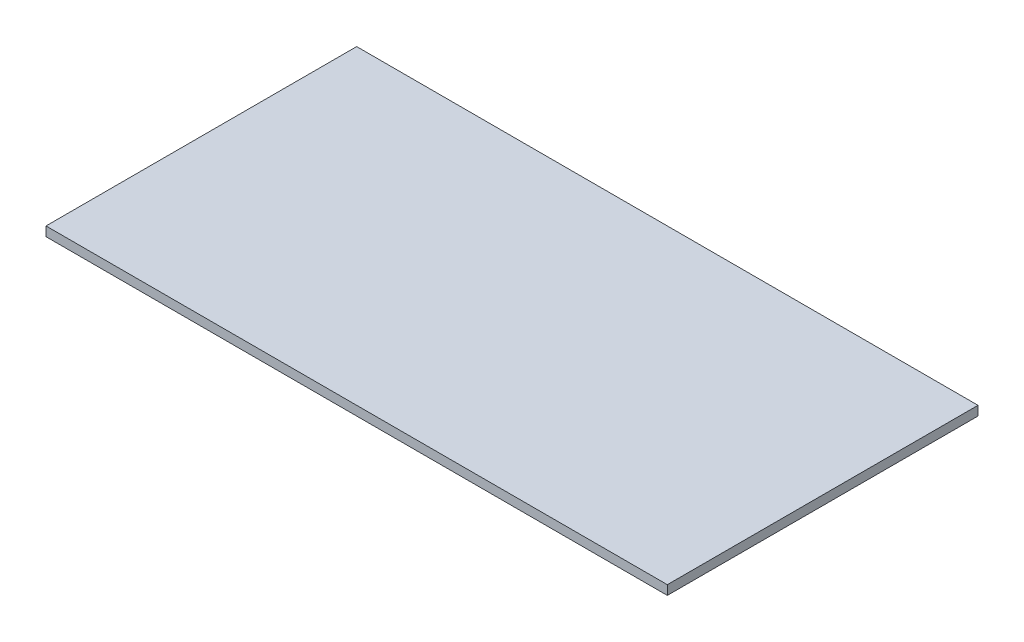
SolidWorks part; units mm, degrees
ref_plane "Спереди" through (0, 0, 0) normal (0, 0, 1) x (1, 0, 0)
ref_plane "Сверху" through (0, 0, 0) normal (0, 1, 0) x (1, 0, 0)
ref_plane "Справа" through (0, 0, 0) normal (1, 0, 0) x (0, 0, -1)
sketch "Эскиз1" plane through (0, 0, 0) normal (0, 1, 0) x (1, 0, 0)
  line L1 (-100, -50) -> (100, -50)
  line L2 (-100, -50) -> (-100, 50)
  line L3 (-100, 50) -> (100, 50)
  line L4 (100, -50) -> (100, 50)
  line L5 (-100, -50) -> (100, 50) construction
  line L6 (-100, 50) -> (100, -50) construction
  point P0 (0, 0)
extrude "CS_BASE" add sketch "Эскиз1" along normal blind 3
ref_plane "Плоскость1" through (-40, 0, 0) normal (-1, 0, 0) x (0, 0, 1)
ref_axis "Ось2" through (-40, 3, 55) along (0, 0, -1)
